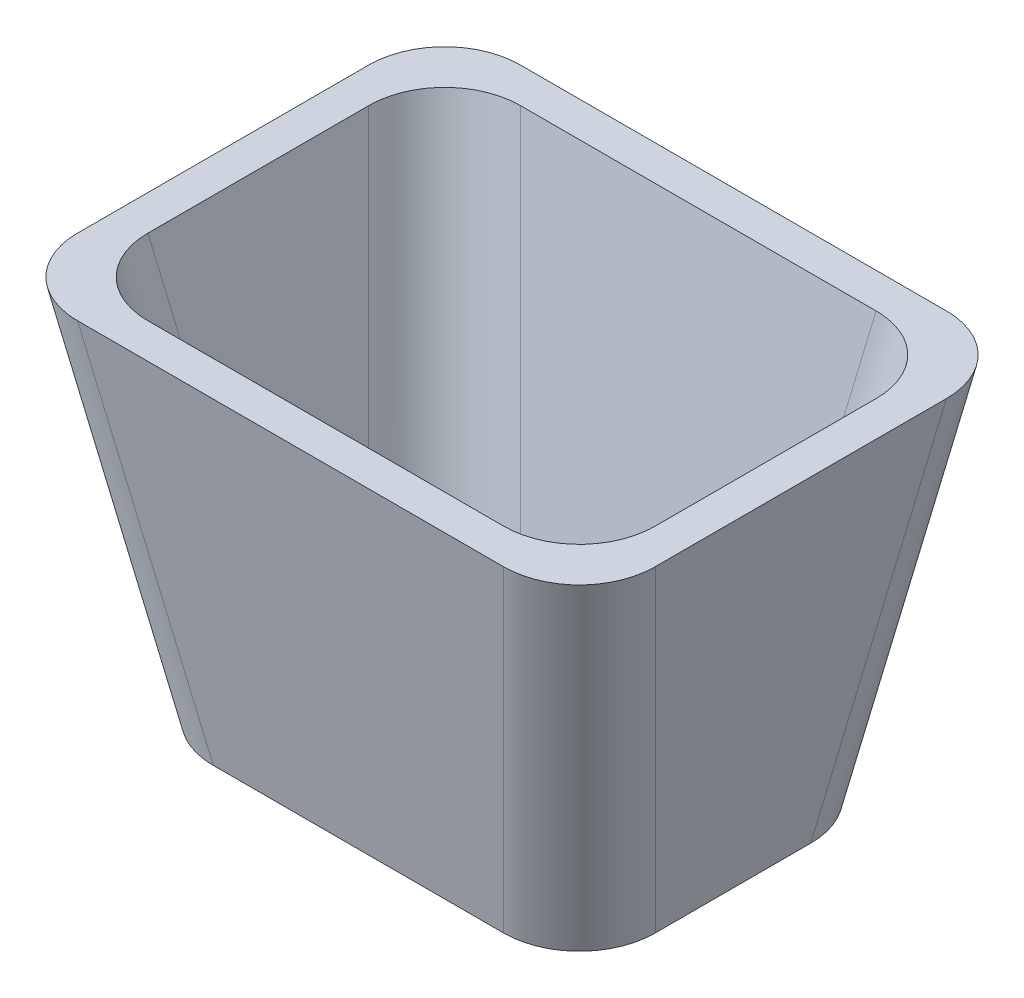
SolidWorks part; units mm, degrees
ref_plane "Front Plane" through (0, 0, 0) normal (0, 0, 1) x (1, 0, 0)
ref_plane "Top Plane" through (0, 0, 0) normal (0, 1, 0) x (1, 0, 0)
ref_plane "Right Plane" through (0, 0, 0) normal (1, 0, 0) x (0, 0, -1)
sketch "Sketch1" plane through (0, 0, 0) normal (0, 1, 0) x (1, 0, 0)
  line L0 (0, 0) -> (0, 14.605) construction
  line L1 (-19.05, 14.605) -> (19.05, 14.605)
  line L2 (-19.05, 14.605) -> (-19.05, -14.605)
  line L3 (-19.05, -14.605) -> (19.05, -14.605)
  line L4 (19.05, 14.605) -> (19.05, -14.605)
  line L5 (0, 0) -> (19.05, 0) construction
  dimension "D1" = 38.1
  dimension "D2" = 29.21
extrude "Boss-Extrude1" add sketch "Sketch1" along normal blind 25.4
sketch "Sketch2" plane through (0, 25.4, 0) normal (0, 1, 0) x (1, 0, 0)
  line L0 (0, 0) -> (0, 8.255) construction
  line L1 (-12.7, 8.255) -> (12.7, 8.255)
  line L2 (-12.7, 8.255) -> (-12.7, -8.255)
  line L3 (-12.7, -8.255) -> (12.7, -8.255)
  line L4 (12.7, 8.255) -> (12.7, -8.255)
  line L5 (0, 0) -> (12.7, 0) construction
  line L6 (-12.7, 0) -> (-19.05, 0) construction
  line L7 (-19.05, 14.605) -> (-19.05, -14.605) construction
  line L8 (0, 8.255) -> (0, 14.605) construction
  line L9 (19.05, 14.605) -> (-19.05, 14.605) construction
  dimension "D1" = 6.35
extrude "Cut-Extrude1" cut sketch "Sketch2" against normal blind 22.86
draft "Draft1" type of draft neutral plane draft angle 10 faces to draft 4 face at (12.7, 13.97, 0) face at (0, 13.97, 8.255) face at (-12.7, 13.97, 0) face at (0, 13.97, -8.255) neutral plane through (0, 2.54, 0) neutral plane normal (0, 1, 0) parameters "D1"=10
draft "Draft2" type of draft neutral plane draft angle 10 faces to draft 4 face at (-19.05, 12.7, 0) face at (0, 12.7, 14.605) face at (19.05, 12.7, 0) face at (0, 12.7, -14.605) neutral plane through (0, 25.4, 0) neutral plane normal (0, 1, 0) reverse direction yes parameters "D1"=10
sketch "Sketch3" plane through (0, 2.54, 0) normal (0, 1, 0) x (1, 0, 0)
  line L2 (0, -0.635) -> (0, -8.255) construction
  line L3 (-12.7, -8.255) -> (12.7, -8.255) construction
  line L4 (-12.7, -8.255) -> (12.7, -8.255)
  line L5 (12.7, -8.255) -> (12.7, 8.255)
  line L6 (12.7, 8.255) -> (-12.7, 8.255)
  line L7 (-12.7, 8.255) -> (-12.7, -8.255)
  line L9 (12.7, -8.255) -> (12.7, 8.255)
  line L10 (12.7, 8.255) -> (-12.7, 8.255)
  line L11 (-12.7, 8.255) -> (-12.7, -8.255)
  line L12 (0, -0.635) -> (-9.525, -8.255)
  line L13 (-12.7, -8.255) -> (12.7, -8.255) construction
  line L14 (0, -0.635) -> (9.525, -8.255)
  line L15 (-12.7, -8.255) -> (-9.525, -8.255)
  line L16 (9.525, -8.255) -> (12.7, -8.255)
  dimension "D2" = 7.62
  dimension "D3" = 19.05
  dimension "D1" = 0
extrude "Cut-Extrude2" cut sketch "Sketch3" against normal blind 22.86
sketch "Sketch5" plane through (0, 0, 0) normal (0, -1, 0) x (1, 0, 0)
  line L0 (0, 5.207) -> (0, 0) construction
  line L1 (-9.525, 8.255) -> (9.525, 8.255) construction
  line L2 (0, 8.255) -> (0, 5.207) construction
  circle A1 centre (0, 5.207) radius 1.651
  dimension "D2" = 3.302
  dimension "D3" = 3.048
extrude "Cut-Extrude3" cut sketch "Sketch5" against normal through all
fillet "Fillet4" radius 2.54 1 edges at (0, 1.27, 0.635)
fillet "Fillet1" radius 5.08 8 edges at (-16.8106, 12.7, 12.3656) (16.8106, 12.7, 12.3656) (16.8106, 12.7, -12.3656) (-16.8106, 12.7, -12.3656) (14.7154, 13.97, 10.2704) (-14.7154, 13.97, 10.2704) (14.7154, 13.97, -10.2704) (-14.7154, 13.97, -10.2704)
fillet "Fillet2" radius 5.08 4 edges at (12.7, 5.3994, -8.255) (-12.7, 5.3994, -8.255) (9.525, 1.9787, 8.255) (-9.525, 1.9787, 8.255)
fillet "Fillet5" radius 5.08 2 edges at (12.7, 5.3994, 8.255) (-12.7, 5.3994, 8.255)
fillet "Fillet6" radius 2.54 2 edges at (11.307, 3.6236, 8.255) (-11.307, 3.6236, 8.255)
